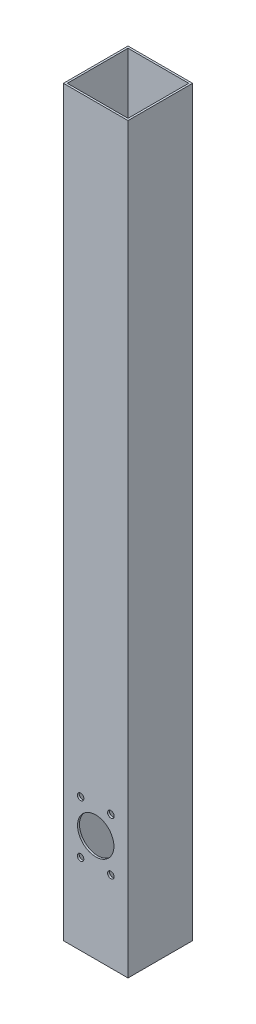
SolidWorks part; units mm, degrees
material "6061 Alloy"
ref_plane "Front Plane" through (0, 0, 0) normal (0, 0, 1) x (1, 0, 0)
ref_plane "Top Plane" through (0, 0, 0) normal (0, 1, 0) x (1, 0, 0)
ref_plane "Right Plane" through (0, 0, 0) normal (1, 0, 0) x (0, 0, -1)
sketch "Sketch1" plane through (0, 0, 0) normal (0, 1, 0) x (1, 0, 0)
  line L1 (25.4, 25.4) -> (-25.4, 25.4)
  line L2 (25.4, 25.4) -> (25.4, -25.4)
  line L3 (25.4, -25.4) -> (-25.4, -25.4)
  line L4 (-25.4, 25.4) -> (-25.4, -25.4)
  line L5 (25.4, 25.4) -> (-25.4, -25.4) construction
  line L6 (25.4, -25.4) -> (-25.4, 25.4) construction
  point P0 (0, 0)
  dimension "D1" = 50.8
extrude "Extrude-Thin1" add sketch "Sketch1" along normal blind 584.2 thin thin type one direction reverse wall 1.524
sketch "Sketch2" plane through (0, 0, 0) normal (0, 0, 1) x (1, 0, 0)
  line L0 (-36.2563, 101.6) -> (38.5702, 101.6) construction
  line L2 (-25.4, 84.1375) -> (25.4, 84.1375) construction
  line L5 (-25.4, 0) -> (25.4, 0) construction
  line L6 (25.4, 584.2) -> (25.4, 0) construction
  line L7 (-25.4, 584.2) -> (-25.4, 0) construction
  line L8 (-11.9126, 63.5043) -> (11.9126, 63.5043) construction
  line L9 (-11.9126, 104.7707) -> (11.9126, 104.7707) construction
  circle A0 centre (0, 84.1375) radius 14.3002
  circle A1 centre (0, 84.1375) radius 23.8252 construction
  circle A2 centre (-11.9126, 63.5043) radius 2.5908
  circle A3 centre (11.9126, 63.5043) radius 2.5908
  circle A4 centre (11.9126, 104.7707) radius 2.5908
  circle A5 centre (-11.9126, 104.7707) radius 2.5908
  point P11 (0, 84.1375)
  dimension "D1" = 28.6004
  dimension "D3" = 17.4625
  dimension "D4" = 47.6504
  dimension "D6" = 5.1816
  dimension "D2" = 101.6
  dimension "D5" = 23.8252
extrude "Cut-Extrude1" cut sketch "Sketch2" along normal through all both and the other way through all
